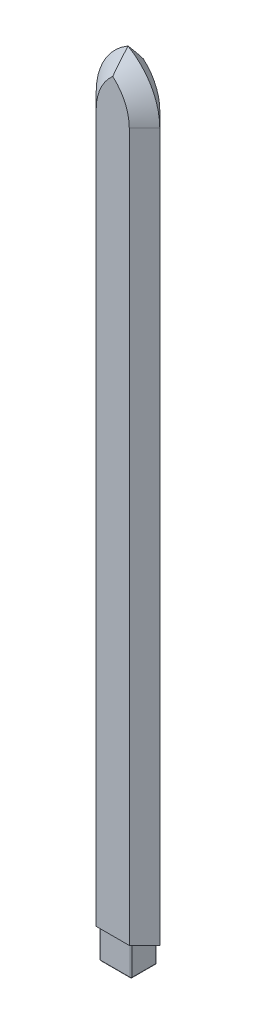
SolidWorks part; units mm, degrees
material "Plain Carbon Steel"
ref_plane "Front Plane" through (0, 0, 0) normal (0, 0, 1) x (1, 0, 0)
ref_plane "Top Plane" through (0, 0, 0) normal (0, 1, 0) x (1, 0, 0)
ref_plane "Right Plane" through (0, 0, 0) normal (1, 0, 0) x (0, 0, -1)
sketch "Sketch1" plane through (0, 0, 0) normal (0, 0, 1) x (1, 0, 0)
  line L1 (-12.7, 0) -> (-12.7, 282.8036)
  line L2 (12.7, 282.8036) -> (12.7, 0)
  line L3 (12.7, 0) -> (-12.7, 0)
  arc A0 (-12.7, 282.8036) -> (0, 304.8006) centre (12.7, 282.8036) cw
  arc A1 (0, 304.8006) -> (12.7, 282.8036) centre (-12.7, 282.8036) cw
  point P0 (0, 0)
  dimension "D1" = 21.997
  dimension "D3" = 25.4
  dimension "D2" = 25.4
  dimension "D4" = 282.8036
extrude "Boss-Extrude1" add sketch "Sketch1" along normal mid plane 12.192
chamfer "Chamfer1" distance 6.096 angle 45 8 edges at (-9.297, 295.5036, -6.096) (-12.7, 141.4018, -6.096) (-9.297, 295.5036, 6.096) (-12.7, 141.4018, 6.096) (9.297, 295.5036, 6.096) (12.7, 141.4018, 6.096) (9.297, 295.5036, -6.096) (12.7, 141.4018, -6.096)
sketch "Sketch2" plane through (0, 0, 0) normal (0, -1, 0) x (1, 0, 0)
  line L0 (-6.604, 6.096) -> (6.604, 6.096) construction
  line L1 (-6.35, -5.08) -> (6.35, -5.08)
  line L2 (-6.35, -5.08) -> (-6.35, 5.08)
  line L3 (-6.35, 5.08) -> (6.35, 5.08)
  line L4 (6.35, -5.08) -> (6.35, 5.08)
  line L5 (-6.35, -5.08) -> (6.35, 5.08) construction
  line L6 (-6.35, 5.08) -> (6.35, -5.08) construction
  point P0 (0, 0)
  dimension "D1" = 12.7
  dimension "D2" = 1.016
  dimension "D3" = 10.16
extrude "Boss-Extrude2" add sketch "Sketch2" along normal blind 12.192
fillet "Fillet2" radius 0.381 12 edges at (0, -12.192, 5.08) (0, 0, 5.08) (6.35, -12.192, 0) (6.35, -6.096, 5.08) (6.35, 0, 0) (0, -12.192, -5.08) (6.35, -6.096, -5.08) (0, 0, -5.08) (-6.35, -6.096, 5.08) (-6.35, -12.192, 0) (-6.35, -6.096, -5.08) (-6.35, 0, 0)
sketch "Sketch3" plane through (0, -12.192, 0) normal (0, -1, 0) x (1, 0, 0)
  circle A0 centre (0, 0) radius 4.7625
  dimension "D1" = 9.525
extrude "Cut-Extrude1" cut sketch "Sketch3" against normal blind 292.1
